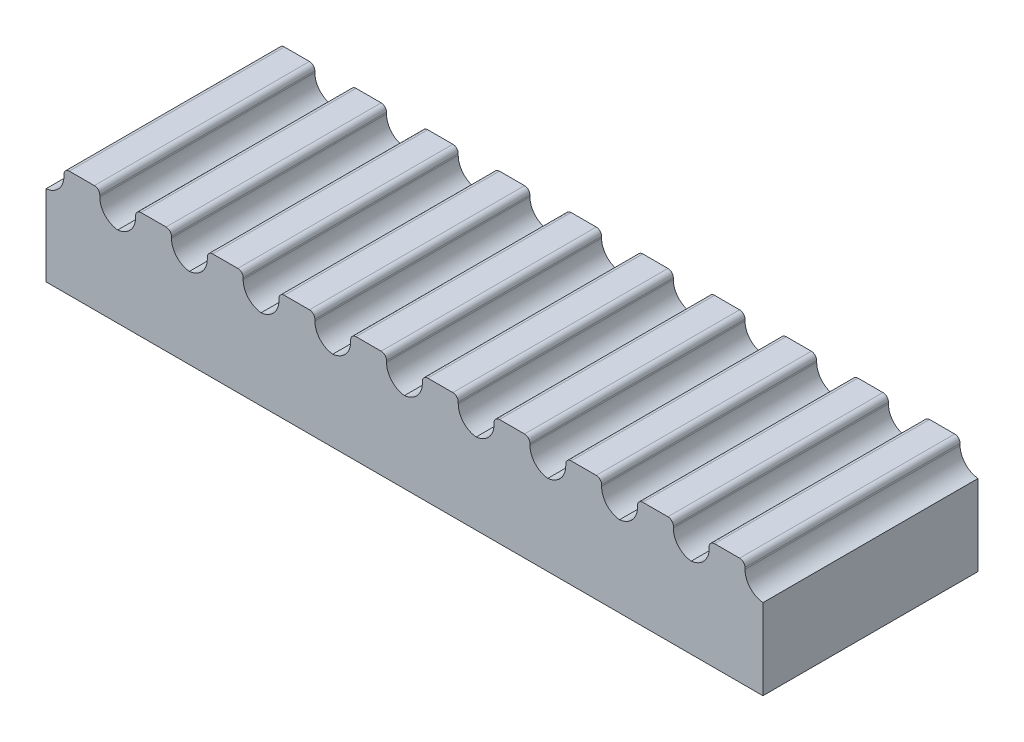
SolidWorks part; units mm, degrees
ref_plane "Front Plane" through (0, 0, 0) normal (0, 0, 1) x (1, 0, 0)
ref_plane "Top Plane" through (0, 0, 0) normal (0, 1, 0) x (1, 0, 0)
ref_plane "Right Plane" through (0, 0, 0) normal (1, 0, 0) x (0, 0, -1)
sketch "Sketch1" plane through (0, 0, 0) normal (0, 1, 0) x (1, 0, 0)
  line L1 (-10, -3) -> (10, -3)
  line L2 (-10, -3) -> (-10, 3)
  line L3 (-10, 3) -> (10, 3)
  line L4 (10, -3) -> (10, 3)
  line L5 (-10, -3) -> (10, 3) construction
  line L6 (-10, 3) -> (10, -3) construction
  point P0 (0, 0)
  dimension "D1" = 6
  dimension "D2" = 20
extrude "Boss-Extrude1" add sketch "Sketch1" along normal blind 3
sketch "Sketch2" plane through (0, 3, 0) normal (0, 1, 0) x (1, 0, 0)
  line L5 (10, 3) -> (-10, 3) construction
  line L6 (-0.5, -3) -> (0.5, -3)
  line L11 (-0.5, -3) -> (-0.5, 3)
  line L12 (-0.5, 3) -> (0.5, 3)
  line L17 (0.5, -3) -> (0.5, 3)
  line L18 (-0.5, -3) -> (0.5, 3) construction
  line L23 (-0.5, 3) -> (0.5, -3) construction
  line L24 (1.5, -3) -> (2.5, -3)
  line L29 (1.5, -3) -> (1.5, 3)
  line L30 (1.5, 3) -> (2.5, 3)
  line L35 (2.5, -3) -> (2.5, 3)
  line L36 (1.5, -3) -> (2.5, 3) construction
  line L41 (1.5, 3) -> (2.5, -3) construction
  line L42 (3.5, -3) -> (4.5, -3)
  line L47 (3.5, -3) -> (3.5, 3)
  line L48 (3.5, 3) -> (4.5, 3)
  line L53 (4.5, -3) -> (4.5, 3)
  line L54 (3.5, -3) -> (4.5, 3) construction
  line L59 (3.5, 3) -> (4.5, -3) construction
  line L60 (5.5, -3) -> (6.5, -3)
  line L65 (5.5, -3) -> (5.5, 3)
  line L66 (5.5, 3) -> (6.5, 3)
  line L71 (6.5, -3) -> (6.5, 3)
  line L72 (5.5, -3) -> (6.5, 3) construction
  line L73 (5.5, 3) -> (6.5, -3) construction
  line L74 (7.5, -3) -> (8.5, -3)
  line L75 (7.5, -3) -> (7.5, 3)
  line L76 (7.5, 3) -> (8.5, 3)
  line L77 (8.5, -3) -> (8.5, 3)
  line L78 (7.5, -3) -> (8.5, 3) construction
  line L79 (7.5, 3) -> (8.5, -3) construction
  line L80 (9.5, -3) -> (10.5, -3)
  line L81 (9.5, -3) -> (9.5, 3)
  line L82 (9.5, 3) -> (10.5, 3)
  line L83 (10.5, -3) -> (10.5, 3)
  line L84 (9.5, -3) -> (10.5, 3) construction
  line L85 (9.5, 3) -> (10.5, -3) construction
  line L86 (-2.5, -3) -> (-1.5, -3)
  line L87 (-2.5, -3) -> (-2.5, 3)
  line L88 (-2.5, 3) -> (-1.5, 3)
  line L89 (-1.5, -3) -> (-1.5, 3)
  line L90 (-2.5, -3) -> (-1.5, 3) construction
  line L91 (-2.5, 3) -> (-1.5, -3) construction
  line L92 (-4.5, -3) -> (-3.5, -3)
  line L93 (-4.5, -3) -> (-4.5, 3)
  line L94 (-4.5, 3) -> (-3.5, 3)
  line L95 (-3.5, -3) -> (-3.5, 3)
  line L96 (-4.5, -3) -> (-3.5, 3) construction
  line L97 (-4.5, 3) -> (-3.5, -3) construction
  line L98 (-6.5, -3) -> (-5.5, -3)
  line L99 (-6.5, -3) -> (-6.5, 3)
  line L100 (-6.5, 3) -> (-5.5, 3)
  line L101 (-5.5, -3) -> (-5.5, 3)
  line L102 (-6.5, -3) -> (-5.5, 3) construction
  line L103 (-6.5, 3) -> (-5.5, -3) construction
  line L104 (-8.5, -3) -> (-7.5, -3)
  line L105 (-8.5, -3) -> (-8.5, 3)
  line L106 (-8.5, 3) -> (-7.5, 3)
  line L107 (-7.5, -3) -> (-7.5, 3)
  line L108 (-8.5, -3) -> (-7.5, 3) construction
  line L109 (-8.5, 3) -> (-7.5, -3) construction
  line L110 (-10.5, -3) -> (-9.5, -3)
  line L111 (-10.5, -3) -> (-10.5, 3)
  line L112 (-10.5, 3) -> (-9.5, 3)
  line L113 (-9.5, -3) -> (-9.5, 3)
  line L114 (-10.5, -3) -> (-9.5, 3) construction
  line L115 (-10.5, 3) -> (-9.5, -3) construction
  point P0 (0, 0)
  point P9 (2, 0)
  point P14 (4, 0)
  point P19 (6, 0)
  point P24 (8, 0)
  point P29 (10, 0)
  point P34 (-2, 0)
  point P39 (-4, 0)
  point P44 (-6, 0)
  point P49 (-8, 0)
  point P54 (-10, 0)
  dimension "D1" = 1
extrude "Cut-Extrude1" cut sketch "Sketch2" against normal blind 0.75
fillet "Fillet1" radius 0.15 20 edges at (-8.5, 3, 0) (-6.5, 3, 0) (-4.5, 3, 0) (-2.5, 3, 0) (-0.5, 3, 0) (1.5, 3, 0) (3.5, 3, 0) (5.5, 3, 0) (7.5, 3, 0) (9.5, 3, 0) (8.5, 3, 0) (6.5, 3, 0) (4.5, 3, 0) (2.5, 3, 0) (0.5, 3, 0) (-1.5, 3, 0) (-3.5, 3, 0) (-5.5, 3, 0) (-7.5, 3, 0) (-9.5, 3, 0)
fillet "Fillet2" radius 0.555 20 edges at (-8.5, 2.25, 0) (-6.5, 2.25, 0) (-4.5, 2.25, 0) (-2.5, 2.25, 0) (-0.5, 2.25, 0) (1.5, 2.25, 0) (3.5, 2.25, 0) (5.5, 2.25, 0) (7.5, 2.25, 0) (9.5, 2.25, 0) (8.5, 2.25, 0) (6.5, 2.25, 0) (4.5, 2.25, 0) (2.5, 2.25, 0) (0.5, 2.25, 0) (-1.5, 2.25, 0) (-3.5, 2.25, 0) (-5.5, 2.25, 0) (-7.5, 2.25, 0) (-9.5, 2.25, 0)
